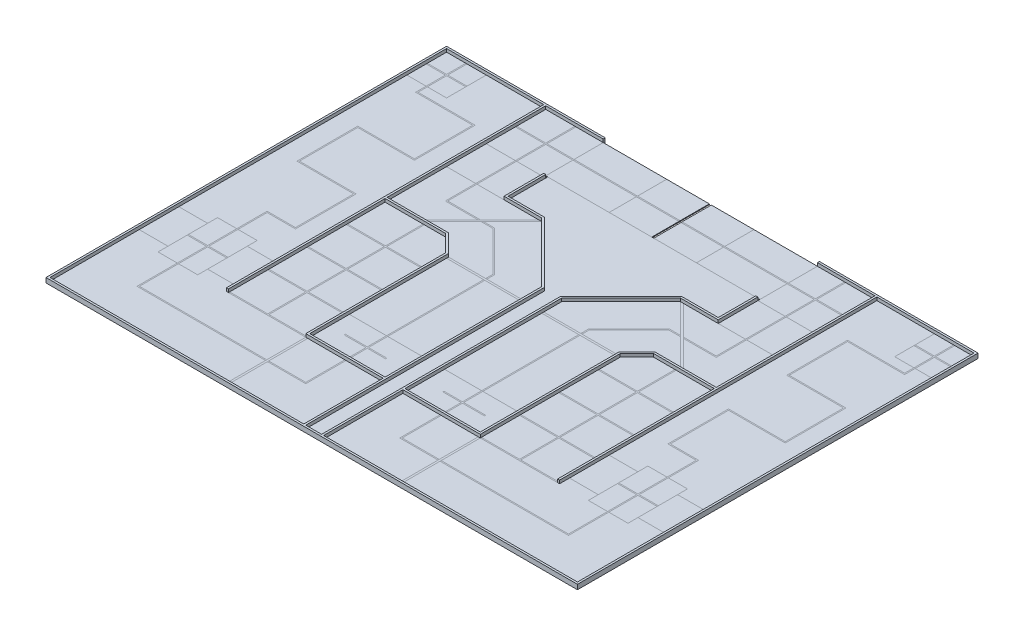
SolidWorks part; units mm, degrees
ref_plane "Front Plane" through (0, 0, 0) normal (0, 0, 1) x (1, 0, 0)
ref_plane "Top Plane" through (0, 0, 0) normal (0, 1, 0) x (1, 0, 0)
ref_plane "Right Plane" through (0, 0, 0) normal (1, 0, 0) x (0, 0, -1)
sketch "Sketch1" plane through (0, 0, 0) normal (0, 1, 0) x (1, 0, 0)
  line L0 (-360.0121, 4738.8338) -> (-6985.0121, 4738.8338)
  line L1 (-6985.0121, 4738.8338) -> (-6985.0121, -5261.1662)
  line L2 (-6985.0121, -5261.1662) -> (-585.0121, -5261.1662)
  line L3 (-585.0121, -5261.1662) -> (-585.0121, 738.8338)
  line L4 (-585.0121, 738.8338) -> (-2085.0121, 2238.8338)
  line L6 (-3035.0121, 3288.8338) -> (-360.0121, 3288.8338)
  line L7 (-360.0121, 3288.8338) -> (-360.0121, 4738.8338)
  line L8 (-2085.0121, 2238.8338) -> (-3035.0121, 2238.8338)
  line L9 (-3035.0121, 2238.8338) -> (-3035.0121, 3288.8338)
  line L10 (-4485.0121, 738.8338) -> (-2935.0121, 738.8338)
  line L11 (-4535.0121, 4738.8338) -> (-4485.0121, 4738.8338)
  line L12 (-4535.0121, 4738.8338) -> (-4535.0121, -3261.1662)
  line L13 (-4535.0121, -3261.1662) -> (-4485.0121, -3261.1662)
  line L14 (-4485.0121, 4738.8338) -> (-4485.0121, -3261.1662)
  line L15 (-2935.0121, 738.8338) -> (-2485.0121, 288.8338)
  line L16 (-2485.0121, 288.8338) -> (-2485.0121, -3261.1662)
  line L17 (-4485.0121, 688.8338) -> (-2955.7227, 688.8338)
  line L18 (-2955.7227, 688.8338) -> (-2535.0121, 268.1231)
  line L19 (-2535.0121, 268.1231) -> (-2535.0121, -3261.1662)
  line L20 (-2535.0121, -3261.1662) -> (-2485.0121, -3261.1662)
  line L21 (-4485.0121, 688.8338) -> (-4485.0121, 738.8338)
  line L22 (-4485.0121, 738.8338) -> (-4485.0121, 2238.8338)
  line L23 (-6985.0121, 4738.8338) -> (-5985.0121, 4738.8338)
  line L24 (-6985.0121, 4738.8338) -> (-6985.0121, 3738.8338)
  line L25 (-6985.0121, 3738.8338) -> (-5985.0121, 3738.8338)
  line L26 (-5985.0121, 4738.8338) -> (-5985.0121, 3738.8338)
  line L27 (-360.0121, 4738.8338) -> (-1435.0121, 4738.8338)
  line L28 (-360.0121, 4738.8338) -> (-360.0121, 3288.8338)
  line L29 (-360.0121, 3288.8338) -> (-1435.0121, 3288.8338)
  line L30 (-1435.0121, 4738.8338) -> (-1435.0121, 3288.8338)
  line L31 (-4485.0121, 4738.8338) -> (-3035.0121, 4738.8338)
  line L32 (-4485.0121, 4738.8338) -> (-4485.0121, 3238.8338)
  line L33 (-4485.0121, 3238.8338) -> (-3035.0121, 3238.8338)
  line L34 (-3035.0121, 4738.8338) -> (-3035.0121, 3238.8338)
  line L35 (-4485.0121, 3238.8338) -> (-3035.0121, 3238.8338)
  line L36 (-4485.0121, 3238.8338) -> (-4485.0121, 2238.8338)
  line L37 (-4485.0121, 2238.8338) -> (-3035.0121, 2238.8338)
  line L38 (-3035.0121, 3238.8338) -> (-3035.0121, 2238.8338)
  line L39 (-2485.0121, -3261.1662) -> (-585.0121, -3261.1662)
  line L40 (-2485.0121, -3261.1662) -> (-2485.0121, -3211.1662)
  line L41 (-2485.0121, -3211.1662) -> (-585.0121, -3211.1662)
  line L42 (-585.0121, -3261.1662) -> (-585.0121, -3211.1662)
  line L43 (-2485.0121, -3211.1662) -> (-585.0121, -3211.1662)
  line L44 (-2485.0121, -3211.1662) -> (-2485.0121, -2211.1662)
  line L45 (-2485.0121, -2211.1662) -> (-585.0121, -2211.1662)
  line L46 (-585.0121, -3211.1662) -> (-585.0121, -2211.1662)
  line L47 (-4485.0121, 2238.8338) -> (-2085.0121, 2238.8338)
  line L48 (-2085.0121, 2238.8338) -> (-585.0121, 738.8338)
  line L49 (-585.0121, 738.8338) -> (-585.0121, -2211.1662)
  line L50 (-585.0121, -2211.1662) -> (-2485.0121, -2211.1662)
  line L51 (-2485.0121, -2211.1662) -> (-2485.0121, 288.8338)
  line L52 (-2485.0121, 288.8338) -> (-2935.0121, 738.8338)
  line L53 (-2935.0121, 738.8338) -> (-4485.0121, 738.8338)
  line L54 (-6260.0121, -2011.1662) -> (-6985.0121, -2011.1662)
  line L59 (-6260.0121, -3261.1662) -> (-5260.0121, -3261.1662)
  line L60 (-6260.0121, -3261.1662) -> (-6260.0121, -1761.1662)
  line L61 (-6260.0121, -1761.1662) -> (-5260.0121, -1761.1662)
  line L62 (-5260.0121, -3261.1662) -> (-5260.0121, -1761.1662)
  line L63 (-6985.0121, -2011.1662) -> (-6985.0121, -3011.1662)
  line L64 (-6985.0121, -3011.1662) -> (-6260.0121, -3011.1662)
  line L65 (-6260.0121, -2011.1662) -> (-6260.0121, -3011.1662)
  line L66 (-5260.0121, -2011.1662) -> (-4535.0121, -2011.1662)
  line L67 (-4535.0121, -2011.1662) -> (-4535.0121, -3011.1662)
  line L68 (-4535.0121, -3011.1662) -> (-5260.0121, -3011.1662)
  line L69 (-5260.0121, -3011.1662) -> (-5260.0121, -2011.1662)
  line L70 (-4485.0121, 3973.8338) -> (-360.0121, 3973.8338)
  line L71 (-360.0121, 3973.8338) -> (-360.0121, 4003.8338)
  line L72 (-360.0121, 4003.8338) -> (-4485.0121, 4003.8338)
  line L73 (-4485.0121, 4003.8338) -> (-4485.0121, 3973.8338)
  line L74 (-3525.0121, 688.8338) -> (-3495.0121, 688.8338)
  line L75 (-3750.0121, 4738.8338) -> (-3720.3456, 4738.8338)
  line L76 (-3750.0121, 4738.8338) -> (-3750.0121, 1480.3446)
  line L78 (-3720.3456, 4738.8338) -> (-3720.3456, 1503.8338)
  line L79 (-4485.0121, -3261.1662) -> (-4542.4551, -3124.551)
  line L80 (-3495.0121, 688.8338) -> (-3495.0121, -261.1662)
  line L81 (-3525.0121, 688.8338) -> (-3525.0121, -261.1662)
  line L82 (-3525.0121, -261.1662) -> (-4485.0121, -261.1662)
  line L83 (-4485.0121, -261.1662) -> (-4485.0121, -291.1662)
  line L84 (-4485.0121, -291.1662) -> (-3525.0121, -291.1662)
  line L85 (-3525.0121, -291.1662) -> (-3525.0121, -1251.1662)
  line L86 (-3495.0121, -261.1662) -> (-2535.0121, -261.1662)
  line L87 (-2535.0121, -261.1662) -> (-2535.0121, -291.1662)
  line L88 (-2535.0121, -291.1662) -> (-3495.0121, -291.1662)
  line L89 (-3495.0121, -291.1662) -> (-3495.0121, -1251.1662)
  line L90 (-3525.0121, -1251.1662) -> (-4485.0121, -1251.1662)
  line L91 (-4485.0121, -1251.1662) -> (-4485.0121, -1281.1662)
  line L92 (-4485.0121, -1281.1662) -> (-3525.0121, -1281.1662)
  line L93 (-3525.0121, -1281.1662) -> (-3525.0121, -2241.1662)
  line L94 (-3525.0121, -2241.1662) -> (-4485.0121, -2241.1662)
  line L95 (-3495.0121, -1251.1662) -> (-2535.0121, -1251.1662)
  line L96 (-2535.0121, -1251.1662) -> (-2535.0121, -1281.1662)
  line L97 (-2535.0121, -1281.1662) -> (-3495.0121, -1281.1662)
  line L98 (-3495.0121, -1281.1662) -> (-3495.0121, -2241.1662)
  line L99 (-4485.0121, -2241.1662) -> (-4485.0121, -2271.1662)
  line L100 (-4485.0121, -2271.1662) -> (-3525.0121, -2271.1662)
  line L101 (-3525.0121, -2271.1662) -> (-3525.0121, -3231.1662)
  line L102 (-3495.0121, -2241.1662) -> (-2535.0121, -2241.1662)
  line L103 (-2535.0121, -2241.1662) -> (-2535.0121, -2271.1662)
  line L104 (-2535.0121, -2271.1662) -> (-3495.0121, -2271.1662)
  line L105 (-3495.0121, -2271.1662) -> (-3495.0121, -3231.1662)
  line L106 (-3525.0121, -3231.1662) -> (-4485.0121, -3231.1662)
  line L107 (-4485.0121, -3231.1662) -> (-4485.0121, -3261.1662)
  line L108 (-4485.0121, -3261.1662) -> (-2535.0121, -3261.1662)
  line L109 (-2535.0121, -3261.1662) -> (-2535.0121, -3231.1662)
  line L110 (-2535.0121, -3231.1662) -> (-3495.0121, -3231.1662)
  line L111 (-2535.0121, -3261.1662) -> (-2535.0121, -5261.1662)
  line L112 (-2535.0121, -5261.1662) -> (-2485.0121, -5261.1662)
  line L113 (-2485.0121, -5261.1662) -> (-2485.0121, -3261.1662)
  line L114 (-2485.0121, -3261.1662) -> (-2535.0121, -3261.1662)
  line L115 (-1550.0121, -3261.1662) -> (-1550.0121, -4246.1662)
  line L116 (-1550.0121, -4246.1662) -> (-2485.0121, -4246.1662)
  line L117 (-1520.0121, -3261.1662) -> (-1520.0121, -4276.1662)
  line L118 (-1520.0121, -4276.1662) -> (-2485.0121, -4276.1662)
  line L119 (-1550.0121, -3261.1662) -> (-1520.0121, -3261.1662)
  line L120 (-2485.0121, -4246.1662) -> (-2485.0121, -4276.1662)
  line L121 (-2535.0121, -4276.1662) -> (-5775.0121, -4276.1662)
  line L122 (-5775.0121, -4276.1662) -> (-5775.0121, -3261.1662)
  line L123 (-2535.0121, -4246.1662) -> (-5745.0121, -4246.1662)
  line L124 (-5745.0121, -4246.1662) -> (-5745.0121, -3261.1662)
  line L125 (-5775.0121, -3261.1662) -> (-5745.0121, -3261.1662)
  line L126 (-2535.0121, -4276.1662) -> (-2535.0121, -4246.1662)
  line L127 (-6260.0121, -2526.1662) -> (-5775.0121, -2526.1662)
  line L128 (-5775.0121, -2526.1662) -> (-5775.0121, -3261.1662)
  line L129 (-5775.0121, -3261.1662) -> (-5745.0121, -3261.1662)
  line L130 (-5745.0121, -3261.1662) -> (-5745.0121, -2526.1662)
  line L131 (-5745.0121, -2526.1662) -> (-5260.0121, -2526.1662)
  line L132 (-5260.0121, -2526.1662) -> (-5260.0121, -2496.1662)
  line L133 (-5260.0121, -2496.1662) -> (-5745.0121, -2496.1662)
  line L134 (-5745.0121, -2496.1662) -> (-5745.0121, -1761.1662)
  line L135 (-5745.0121, -1761.1662) -> (-5775.0121, -1761.1662)
  line L136 (-5775.0121, -1761.1662) -> (-5775.0121, -2496.1662)
  line L137 (-5775.0121, -2496.1662) -> (-6260.0121, -2496.1662)
  line L138 (-6260.0121, -2496.1662) -> (-6260.0121, -2526.1662)
  line L139 (-6500.0121, 4738.8338) -> (-6500.0121, 4253.8338)
  line L140 (-6500.0121, 4253.8338) -> (-6985.0121, 4253.8338)
  line L141 (-6985.0121, 4253.8338) -> (-6985.0121, 4223.8338)
  line L142 (-6985.0121, 4223.8338) -> (-6500.0121, 4223.8338)
  line L143 (-6500.0121, 4223.8338) -> (-6500.0121, 3738.8338)
  line L144 (-6500.0121, 3738.8338) -> (-6470.0121, 3738.8338)
  line L145 (-6470.0121, 3738.8338) -> (-6470.0121, 4223.8338)
  line L146 (-6470.0121, 4223.8338) -> (-5985.0121, 4223.8338)
  line L147 (-5985.0121, 4223.8338) -> (-5985.0121, 4253.8338)
  line L148 (-5985.0121, 4253.8338) -> (-6470.0121, 4253.8338)
  line L149 (-6470.0121, 4253.8338) -> (-6470.0121, 4738.8338)
  line L150 (-6470.0121, 4738.8338) -> (-6500.0121, 4738.8338)
  line L151 (-6500.0121, 3473.8338) -> (-5060.0121, 3473.8338)
  line L152 (-5060.0121, 3473.8338) -> (-5060.0121, 2003.8338)
  line L153 (-5060.0121, 2003.8338) -> (-6490.0121, 2003.8338)
  line L154 (-6500.0121, 3738.8338) -> (-6500.0121, 3473.8338)
  line L155 (-6490.0121, 2003.8338) -> (-6490.0121, 473.8338)
  line L156 (-6490.0121, 473.8338) -> (-5060.0121, 473.8338)
  line L157 (-5060.0121, 473.8338) -> (-5060.0121, -996.1662)
  line L158 (-5060.0121, -996.1662) -> (-5775.0121, -996.1662)
  line L159 (-5775.0121, -996.1662) -> (-5775.0121, -1761.1662)
  line L160 (-6470.0121, 3738.8338) -> (-6470.0121, 3503.8338)
  line L161 (-6470.0121, 3503.8338) -> (-5030.0121, 3503.8338)
  line L162 (-5030.0121, 3503.8338) -> (-5030.0121, 1973.8338)
  line L163 (-5030.0121, 1973.8338) -> (-6460.0121, 1973.8338)
  line L164 (-6460.0121, 1973.8338) -> (-6460.0121, 503.8338)
  line L165 (-6460.0121, 503.8338) -> (-5030.0121, 503.8338)
  line L166 (-5030.0121, 503.8338) -> (-5030.0121, -1026.1662)
  line L167 (-5030.0121, -1026.1662) -> (-5745.0121, -1026.1662)
  line L168 (-5745.0121, -1026.1662) -> (-5745.0121, -1761.1662)
  line L169 (-6500.0121, 3738.8338) -> (-6470.0121, 3738.8338)
  line L170 (-5775.0121, -1761.1662) -> (-5745.0121, -1761.1662)
  line L171 (-2085.0121, 2238.8338) -> (-3585.0121, 738.8338)
  line L172 (-2155.7227, 2238.8338) -> (-3620.3674, 774.1892)
  line L173 (-2085.0121, 2238.8338) -> (-2155.7227, 2238.8338)
  line L174 (-2120.3674, 2274.1892) -> (-3620.3674, 774.1892) construction
  line L175 (-3620.3674, 774.1892) -> (-3655.7227, 738.8338)
  line L176 (-3655.7227, 738.8338) -> (-3585.0121, 738.8338)
  line L177 (-2485.0121, 288.8338) -> (-585.0121, 288.8338)
  line L178 (-2485.0121, 238.8338) -> (-585.0121, 238.8338)
  line L179 (-2485.0121, 288.8338) -> (-2485.0121, 238.8338)
  line L180 (-585.0121, 288.8338) -> (-585.0121, 238.8338)
  line L181 (-1550.0121, -3211.1662) -> (-1550.0121, -2726.1662)
  line L182 (-1550.0121, -2726.1662) -> (-2102.61, -2726.1662)
  line L183 (-2102.61, -2726.1662) -> (-2102.61, -2696.1662)
  line L184 (-2102.61, -2696.1662) -> (-1550.0121, -2696.1662)
  line L185 (-1550.0121, -2696.1662) -> (-1550.0121, 238.8338)
  line L186 (-1550.0121, 238.8338) -> (-1520.0121, 238.8338)
  line L187 (-1520.0121, 238.8338) -> (-1520.0121, -2696.1662)
  line L188 (-1520.0121, -2696.1662) -> (-1056.1012, -2696.1662)
  line L189 (-1056.1012, -2696.1662) -> (-1056.1012, -2726.1662)
  line L190 (-1056.1012, -2726.1662) -> (-1520.0121, -2726.1662)
  line L191 (-1520.0121, -2726.1662) -> (-1520.0121, -3211.1662)
  line L192 (-1520.0121, -3211.1662) -> (-1550.0121, -3211.1662)
  line L193 (-3720.3456, 1503.8338) -> (-2890.7227, 1503.8338)
  line L194 (-2890.7227, 1503.8338) -> (-2920.7227, 1473.8338)
  line L195 (-2920.7227, 1473.8338) -> (-3750.0121, 1473.8338)
  line L196 (-3750.0121, 1473.8338) -> (-3750.0121, 1480.3446)
  line L197 (-2850.0121, 1473.8338) -> (-2547.4385, 1473.8338)
  line L198 (-2535.0121, 1503.8338) -> (-1520.0121, 488.8338)
  line L199 (-2850.0121, 1473.8338) -> (-2820.0121, 1503.8338)
  line L200 (-2820.0121, 1503.8338) -> (-2535.0121, 1503.8338)
  line L201 (-2547.4385, 1473.8338) -> (-1550.0121, 476.4074)
  line L202 (-1550.0121, 476.4074) -> (-1550.0121, 288.8338)
  line L203 (-1550.0121, 288.8338) -> (-1520.0121, 288.8338)
  line L204 (-1520.0121, 288.8338) -> (-1520.0121, 488.8338)
  line L205 (-3035.0121, 4788.8338) -> (-6985.0121, 4788.8338)
  line L206 (-7035.0121, 4738.8338) -> (-7035.0121, -5311.1662)
  line L207 (-7035.0121, -5311.1662) -> (-535.0121, -5311.1662)
  line L208 (-535.0121, -5311.1662) -> (-535.0121, 738.8338)
  line L209 (-549.6567, 774.1892) -> (-2049.6567, 2274.1892)
  line L210 (-2085.0121, 2288.8338) -> (-2985.0121, 2288.8338)
  line L211 (-2985.0121, 2288.8338) -> (-2985.0121, 3238.8338)
  line L218 (-7035.0121, 4738.8338) -> (-7035.0121, 4788.8338)
  line L219 (-7035.0121, 4788.8338) -> (-6985.0121, 4788.8338)
  line L220 (-535.0121, 738.8338) -> (-535.0121, 759.5445)
  line L221 (-549.6567, 774.1892) -> (-535.0121, 759.5445)
  line L222 (-2085.0121, 2288.8338) -> (-2064.3014, 2288.8338)
  line L223 (-2049.6567, 2274.1892) -> (-2064.3014, 2288.8338)
  line L224 (-2985.0121, 3238.8338) -> (-3035.0121, 3238.8338)
  line L225 (-3035.0121, 4738.8338) -> (-3035.0121, 4788.8338)
  line L226 (-2985.0121, 3238.8338) -> (-360.0121, 3238.8338) construction
  line L227 (-360.0121, 4788.8338) -> (-6985.0121, 4788.8338) construction
  circle A0 centre (-5760.0121, 2738.8338) radius 150.29 construction
  circle A1 centre (-5760.0121, 1238.8338) radius 142.7207 construction
  circle A2 centre (-5760.0121, -261.1662) radius 164.0771 construction
  point P85 (-4485.0121, -2256.1662)
  point P100 (-1535.0121, -3261.1662)
  point P119 (-5260.0121, -2511.1662)
  point P132 (-5985.0121, 4238.8338)
  point P159 (-6485.0121, 3738.8338)
  point P169 (-2485.0121, 263.8338)
  dimension "D1" = 6625
  dimension "D2" = 10000
  dimension "D3" = 6400
  dimension "D4" = 1500
  dimension "D5" = 6000
  dimension "D6" = 1050
  dimension "D7" = 2675
  dimension "D8" = 50
  dimension "D9" = 8000
  dimension "D10" = 0
  dimension "D11" = 2450
  dimension "D12" = 450
  dimension "D13" = 135
  dimension "D14" = 3550
  dimension "D15" = 0
  dimension "D16" = 1550
  dimension "D18" = 1000
  dimension "D19" = 1000
  dimension "D20" = 1075
  dimension "D21" = 1450
  dimension "D22" = 1500
  dimension "D23" = 1450
  dimension "D24" = 1000
  dimension "D25" = 50
  dimension "D26" = 1000
  dimension "D27" = 1000
  dimension "D28" = 1500
  dimension "D29" = 0
  dimension "D30" = 725
  dimension "D31" = 1000
  dimension "D32" = 250
  dimension "D33" = 1000
  dimension "D34" = 735
  dimension "D35" = 30
  dimension "D36" = 735
  dimension "D37" = 735
  dimension "D38" = 30
  dimension "D39" = 0
  dimension "D40" = 960
  dimension "D41" = 950
  dimension "D42" = 950
  dimension "D43" = 30
  dimension "D44" = 30
  dimension "D45" = 0
  dimension "D46" = 0
  dimension "D47" = 30
  dimension "D48" = 0
  dimension "D49" = 960
  dimension "D50" = 960
  dimension "D51" = 30
  dimension "D52" = 30
  dimension "D53" = 0
  dimension "D54" = 0
  dimension "D55" = 30
  dimension "D56" = 0
  dimension "D57" = 960
  dimension "D58" = 960
  dimension "D59" = 30
  dimension "D60" = 0
  dimension "D61" = 0
  dimension "D62" = 30
  dimension "D63" = 960
  dimension "D64" = 960
  dimension "D65" = 0
  dimension "D66" = 30
  dimension "D67" = 0
  dimension "D68" = 0
  dimension "D69" = 50
  dimension "D70" = 0
  dimension "D71" = 0
  dimension "D73" = 935
  dimension "D74" = 985
  dimension "D75" = 0
  dimension "D76" = 0
  dimension "D78" = 1210
  dimension "D79" = 0
  dimension "D80" = 0
  dimension "D81" = 30
  dimension "D82" = 30
  dimension "D83" = 30
  dimension "D84" = 0
  dimension "D85" = 0
  dimension "D86" = 0
  dimension "D87" = 30
  dimension "D88" = 0
  dimension "D89" = 0
  dimension "D90" = 735
  dimension "D91" = 0
  dimension "D92" = 0
  dimension "D93" = 30
  dimension "D94" = 30
  dimension "D95" = 30
  dimension "D96" = 30
  dimension "D97" = 0
  dimension "D98" = 0
  dimension "D99" = 0
  dimension "D100" = 0
  dimension "D101" = 485
  dimension "D102" = 0
  dimension "D103" = 485
  dimension "D104" = 0
  dimension "D105" = 2000
  dimension "D106" = 1225
  dimension "D107" = 1500
  dimension "D108" = 1500
  dimension "D110" = 0
  dimension "D111" = 0
  dimension "D112" = 735
  dimension "D113" = 735
  dimension "D114" = 495
  dimension "D115" = 495
  dimension "D116" = 735
  dimension "D117" = 735
  dimension "D118" = 495
  dimension "D119" = 0
  dimension "D120" = 0
  dimension "D121" = 735
  dimension "D122" = 735
  dimension "D124" = 50
  dimension "D125" = 0
  dimension "D126" = 0
  dimension "D127" = 0
  dimension "D128" = 30
  dimension "D129" = 30
  dimension "D130" = 30
  dimension "D131" = 30
  dimension "D132" = 0
  dimension "D133" = 0
  dimension "D134" = 30
  dimension "D135" = 30
  dimension "D136" = 285
  dimension "D137" = 50
  dimension "D138" = 30
  dimension "D139" = 0
  dimension "D141" = 0
  dimension "D143" = 0
  dimension "D144" = 485
  dimension "D17" = 50
  dimension "D72" = 30
  dimension "D77" = 30
  dimension "D109" = 30
  dimension "D123" = 50
extrude "Boss-Extrude3" add sketch "Sketch1" along normal blind 20 contours L121 L122 L59 L60 L64 L1 L2 L111 | L124 L123 L111 L108 L13 L12 L68 L62 L59 | L117 L118 L113 L2 L3 L39 | L116 L115 L39 L113 | L159 L158 L157 L156 L155 L153 L152 L151 L154 L25 L1 L54 L60 L61 | L167 L168 L61 L62 L66 L12 L0 L26 L25 L160 L161 L162 L163 L164 L165 L166 region at (-5244.5255, 0, -1583.8939) region at (-4181.0808, 0, 3720.1877) region at (-6017.5121, 0, 1700.5294) region at (-2017.5121, 0, 3753.6662) region at (-5161.7593, 0, 4505.5671) region at (-1372.6648, 0, 4432.1951)
extrude "Boss-Extrude4" add sketch "Sketch1<10>" along normal blind 20 separate body contours L1 L64 L60 L65 L54 | L68 L12 L66 L62 L69 region at (-4897.5121, 0, 2511.1662) region at (-6622.5121, 0, 2511.1662)
sketch "Sketch1<10>" plane through (0, 0, 0) normal (0, 1, 0) x (1, 0, 0) same geometry as "Sketch1"
extrude "Boss-Extrude5" add sketch "Sketch1<11>" along normal blind 20 separate body contours L140 L139 L23 L1 | L143 L142 L1 L25 | L149 L148 L26 L0 | L146 L145 L25 L26 | L76 L70 L32 L33 | L76 L0 L14 L72 | L0 L78 L72 L34 | L70 L78 L33 L9 L34 | L70 L30 L6 L7 | L72 L7 L0 L30 | L184 L185 L45 L16 L41 L181 L182 L183 | L190 L191 L41 L3 L45 L187 L188 L189 region at (-897.5121, 0, -4371.3338) region at (-3377.6788, 0, -4371.3338) region at (-897.5121, 0, -3631.3338) region at (-4117.5121, 0, -4371.3338) region at (-3377.6788, 0, -3606.3338) region at (-4117.5121, 0, -3606.3338) region at (-6227.5121, 0, -4496.3338) region at (-6742.5121, 0, -4496.3338) region at (-6227.5121, 0, -3981.3338) region at (-6742.5121, 0, -3981.3338) region at (-2471.3218, 0, 2711.1662) region at (-1048.953, 0, 2711.1662)
sketch "Sketch1<11>" plane through (0, 0, 0) normal (0, 1, 0) x (1, 0, 0) same geometry as "Sketch1"
extrude "Boss-Extrude6" add sketch "Sketch1<12>" along normal blind 20 separate body contours L76 L33 L14 L37 | L33 L78 L37 L9 region at (-3377.6788, 0, -2738.8338) region at (-4117.5121, 0, -2738.8338)
sketch "Sketch1<12>" plane through (0, 0, 0) normal (0, 1, 0) x (1, 0, 0) same geometry as "Sketch1"
extrude "Boss-Extrude7" add sketch "Sketch1<13>" along normal blind 20 separate body contours L195 L196 L76 L37 L14 L10 L175 L172 | L78 L193 L172 L47 L37 | L204 L177 L49 L4 L171 L200 L198 | L202 L201 L197 L171 L53 L15 L177 | L45 L185 L178 L51 | L178 L187 L45 L3 | L70 L34 L6 L30 | L72 L30 L0 L34 region at (-2235.0121, 0, -4371.3338) region at (-2235.0121, 0, -3631.3338) region at (-3102.9813, 0, -1908.9396) region at (-3965.1809, 0, -1421.7442) region at (-1597.6377, 0, -1157.5831) region at (-2493.5321, 0, -824.6132) region at (-1052.5121, 0, 986.1662) region at (-2017.5121, 0, 986.1662)
sketch "Sketch1<13>" plane through (0, 0, 0) normal (0, 1, 0) x (1, 0, 0) same geometry as "Sketch1"
extrude "Boss-Extrude8" add sketch "Sketch1<14>" along normal blind 20 separate body contours L82 L81 L17 L14 | L80 L86 L19 L18 L17 | L90 L85 L84 L14 | L89 L95 L19 L88 | L94 L93 L92 L14 | L98 L102 L19 L97 | L106 L101 L100 L14 | L110 L19 L104 L105 region at (-4005.0121, 0, 2751.1662) region at (-4005.0121, 0, -213.8338) region at (-3015.0121, 0, 2751.1662) region at (-4005.0121, 0, 1761.1662) region at (-4005.0121, 0, 771.1662) region at (-3051.5252, 0, -177.858) region at (-3015.0121, 0, 1761.1662) region at (-3015.0121, 0, 771.1662)
sketch "Sketch1<14>" plane through (0, 0, 0) normal (0, 1, 0) x (1, 0, 0) same geometry as "Sketch1"
extrude "Boss-Extrude9" add sketch "Sketch1<15>" along normal blind 20 separate body contours L137 L136 L61 L60 | L134 L133 L62 L61 | L128 L127 L60 L59 | L131 L130 L59 L62 region at (-5502.5121, 0, 2128.6662) region at (-5502.5121, 0, 2893.6662) region at (-6017.5121, 0, 2128.6662) region at (-6017.5121, 0, 2893.6662)
sketch "Sketch1<15>" plane through (0, 0, 0) normal (0, 1, 0) x (1, 0, 0) same geometry as "Sketch1"
extrude "Boss-Extrude10" add sketch "Sketch1<16>" along normal blind 20 separate body contours L172 L175 L53 L171 L8 | L16 L178 L49 L177 | L114 L111 L112 L113 region at (-2870.3674, 0, -1488.8338) region at (-1535.0121, 0, -263.8338)
sketch "Sketch1<16>" plane through (0, 0, 0) normal (0, 1, 0) x (1, 0, 0) same geometry as "Sketch1"
extrude "Boss-Extrude11" add sketch "Sketch1<20>" along normal blind 20 and the other way blind 2 separate body contours L148 L149 L23 L139 L140 L24 L142 L143 L25 L145 L146 L26 | L168 L167 L166 L165 L164 L163 L162 L161 L160 L25 L154 L151 L152 L153 L155 L156 L157 L158 L159 L61 | L123 L124 L59 L122 L121 L111 | L177 L204 L198 L200 L171 L197 L201 L202 | L196 L195 L172 L193 L78 L47 L76 | L78 L35 L76 L47 | L78 L70 L76 L35 | L76 L72 L32 L70 | L72 L78 L70 L34 | L19 L110 L105 L104 L102 L98 L97 L95 L89 L88 L86 L80 L17 L81 L82 L14 L84 L85 L90 L92 L93 L94 L100 L101 L106 L108 | L134 L135 L136 L137 L138 L127 L128 L129 L130 L131 L132 L133 | L117 L118 L120 L116 L115 L119 | L191 L192 L181 L182 L183 L184 L185 L186 L187 L188 L189 L190 | L78 L193 L194 L195 L196 L76 L75 | L72 L73 L70 L71 region at (-3377.6788, 0, -3988.8338) region at (-4117.5121, 0, -3988.8338) region at (-3735.1788, 0, -3606.3338) region at (-3735.1788, 0, -2738.8338) region at (-3731.8504, 0, -1871.3338) region at (-6485.0121, 0, -4238.8338) region at (-3510.0121, 0, 1599.8377) region at (-5760.0121, 0, 1704.2356) region at (-2677.5121, 0, -1485.8196) region at (-5748.4073, 0, 3753.6662)
sketch "Sketch1<20>" plane through (0, 0, 0) normal (0, 1, 0) x (1, 0, 0) same geometry as "Sketch1"
extrude "Boss-Extrude12" add sketch "Sketch1<22>" along normal blind 100 and the other way blind 20 separate body contours L209 L223 L222 L210 L211 L205 L219 L218 L206 L207 L208 L220 L221 L9 L47 L8 L4 L49 L3 L2 L1 L24 L23 L0 L31 L7 L28 | L12 L11 L14 L13 | L21 L10 L15 L16 L20 L19 L18 L17 | L40 L39 L42 L41 region at (-3377.6788, 0, -4750.8447)
sketch "Sketch1<22>" plane through (0, 0, 0) normal (0, 1, 0) x (1, 0, 0) same geometry as "Sketch1"
ref_plane "Plane1" through (-335.0121, 0, 0) normal (1, 0, 0) x (0, 0, -1)
mirror "Mirror1" about plane through (-335.0121, 0, 0) normal (1, 0, 0) of bodies 113 155 158 156 153 122 154 151 125 118 137 139 126 134 159 127 136 146 128 145 129 130 131 141 142 143 144 132 133 115 116 114 157 117 121 135 140 162 167 149
sketch "Sketch2" plane through (-535.0121, 0, 0) normal (1, 0, 0) x (0, 0, -1)
  line L0 (-5311.1662, -20) -> (759.5445, -20) construction
  line L1 (-5311.1662, 100) -> (-5261.1662, 100)
  line L2 (-5311.1662, 100) -> (-5311.1662, -20)
  line L3 (-5311.1662, -20) -> (-5261.1662, -20)
  line L4 (-5261.1662, 100) -> (-5261.1662, -20)
  line L5 (-5309.1662, 98) -> (-5263.1662, 98)
  line L6 (-5263.1662, 98) -> (-5263.1662, -18)
  line L7 (-5309.1662, -18) -> (-5263.1662, -18)
  line L8 (-5309.1662, 98) -> (-5309.1662, -18)
  dimension "D1" = 50
  dimension "D2" = 2
extrude "Boss-Extrude13" add sketch "Sketch2" along normal up to next (400 mm away)
sketch "Sketch3" plane through (0, 20, 0) normal (0, 1, 0) x (1, 0, 0)
  line L0 (-135.0121, -5261.1662) -> (-135.0121, 759.5445) construction
  line L1 (1394.2773, 2288.8338) -> (-135.0121, 759.5445) construction
  line L2 (-535.0121, -5261.1662) -> (-535.0121, 759.5445) construction
  line L3 (-2064.3014, 2288.8338) -> (-535.0121, 759.5445) construction
  line L4 (-2985.0121, 2288.8338) -> (-2064.3014, 2288.8338) construction
  line L5 (-2985.0121, 2288.8338) -> (-2985.0121, 3238.8338) construction
  line L6 (-135.0121, -5261.1662) -> (-135.0121, 759.5445)
  line L7 (1394.2773, 2288.8338) -> (-135.0121, 759.5445)
  line L8 (-535.0121, -5261.1662) -> (-535.0121, 759.5445)
  line L9 (-2064.3014, 2288.8338) -> (-535.0121, 759.5445)
  line L10 (-2985.0121, 2288.8338) -> (-2064.3014, 2288.8338)
  line L11 (-2985.0121, 2288.8338) -> (-2985.0121, 3288.8338)
  line L12 (-135.0121, -5261.1662) -> (-535.0121, -5261.1662) construction
  line L13 (-135.0121, -5261.1662) -> (-535.0121, -5261.1662)
  line L14 (2314.9879, 2288.8338) -> (1394.2773, 2288.8338) construction
  line L15 (2314.9879, 2288.8338) -> (2314.9879, 3238.8338) construction
  line L16 (1394.2773, 2288.8338) -> (-135.0121, 759.5445)
  line L17 (2314.9879, 2288.8338) -> (1394.2773, 2288.8338)
  line L18 (2314.9879, 2288.8338) -> (2314.9879, 3288.8338)
  line L19 (2364.9879, 3288.8338) -> (764.9879, 3288.8338) construction
  line L20 (764.9879, 3288.8338) -> (-310.0121, 3288.8338) construction
  line L21 (-1435.0121, 3288.8338) -> (-360.0121, 3288.8338) construction
  line L22 (-3035.0121, 3288.8338) -> (-1435.0121, 3288.8338) construction
  line L23 (2314.9879, 3288.8338) -> (764.9879, 3288.8338)
  line L24 (764.9879, 3288.8338) -> (-310.0121, 3288.8338)
  line L25 (-1435.0121, 3288.8338) -> (-310.0121, 3288.8338)
  line L26 (-2985.0121, 3288.8338) -> (-1435.0121, 3288.8338)
  line L27 (2364.9879, 3288.8338) -> (764.9879, 3288.8338) construction
  line L28 (-3035.0121, 3288.8338) -> (-1435.0121, 3288.8338) construction
  point P13 (2314.9879, 3288.8338)
  point P21 (-2985.0121, 3287.1311)
  point P23 (-2985.0121, 3288.8338)
  point P26 (-311.02, 3288.8338)
extrude "Boss-Extrude14" add sketch "Sketch3" against normal blind 20 separate body contours L26 L11 L10 L9 L8 L13 L6 L7 L17 L18 L23 L24 L25 region at (-335.0121, 20, -1356.0116)
